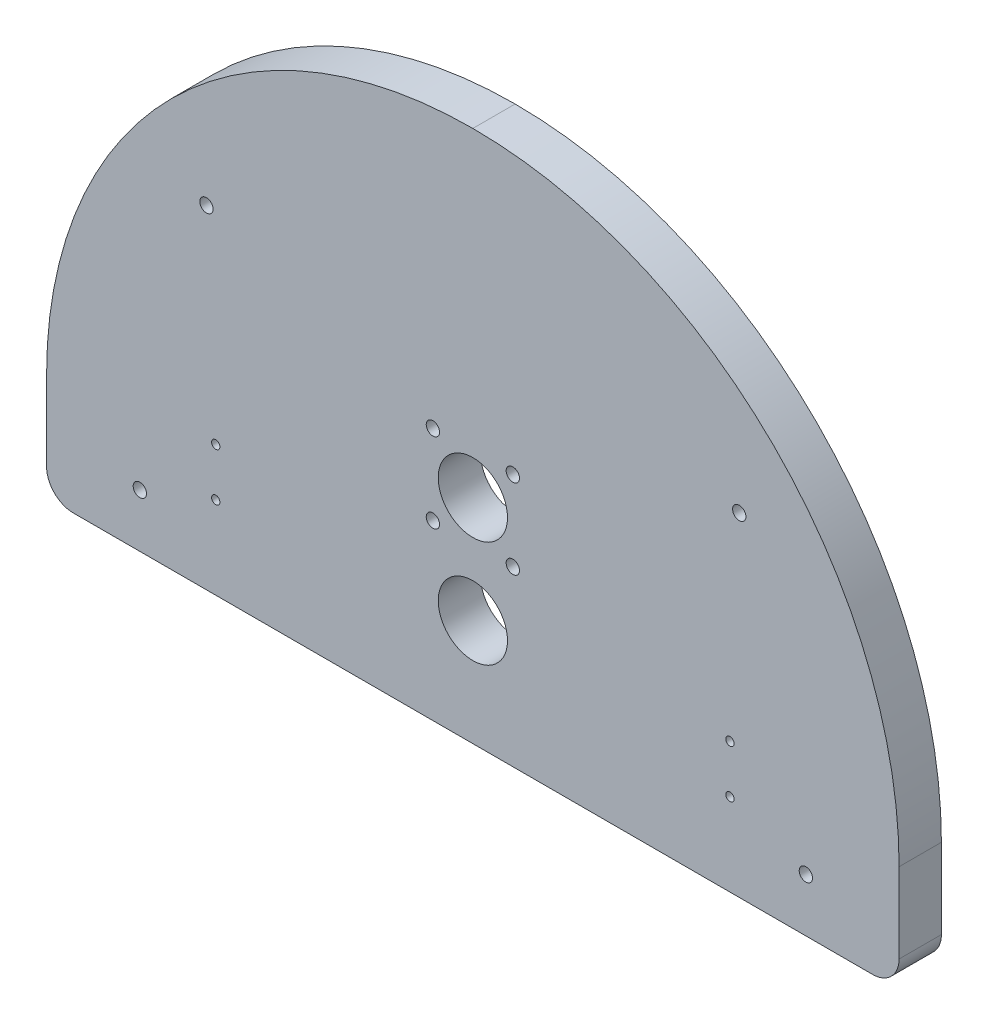
SolidWorks part; units mm, degrees
ref_plane "Front Plane" through (0, 0, 0) normal (0, 0, 1) x (1, 0, 0)
ref_plane "Top Plane" through (0, 0, 0) normal (0, 1, 0) x (1, 0, 0)
ref_plane "Right Plane" through (0, 0, 0) normal (1, 0, 0) x (0, 0, -1)
sketch "Sketch1" plane through (0, 0, 0) normal (0, 0, 1) x (1, 0, 0)
  line L1 (-160, 100) -> (160, 100)
  line L2 (-160, 100) -> (-160, -100)
  line L3 (-160, -100) -> (160, -100)
  line L4 (160, 100) -> (160, -100)
  line L5 (-160, 100) -> (160, -100) construction
  line L6 (-160, -100) -> (160, 100) construction
  point P0 (0, 0)
  dimension "D1" = 320
  dimension "D2" = 200
extrude "Boss-Extrude1" add sketch "Sketch1" along normal blind 15.875
fillet "Fillet1" radius 160 2 edges at (-160, 100, 7.9375) (160, 100, 7.9375)
fillet "Fillet2" radius 10 2 edges at (-160, -100, 7.9375) (160, -100, 7.9375)
sketch "Sketch2" plane through (0, 0, 15.875) normal (0, 0, 1) x (1, 0, 0)
  line L0 (-150, -100) -> (150, -100) construction
  circle A0 centre (0, -60) radius 13
  circle A1 centre (0, -20) radius 13
  dimension "D2" = 40
  dimension "D3" = 26
  dimension "D1" = 40
extrude "Cut-Extrude1" cut sketch "Sketch2" against normal through all
sketch "Sketch3" plane through (0, 0, 15.875) normal (0, 0, 1) x (1, 0, 0)
  line L1 (-15, -35) -> (15, -35) construction
  line L2 (-15, -35) -> (-15, -5) construction
  line L3 (-15, -5) -> (15, -5) construction
  line L4 (15, -35) -> (15, -5) construction
  line L5 (-15, -35) -> (15, -5) construction
  line L6 (-15, -5) -> (15, -35) construction
  circle A0 centre (-15, -5) radius 2.5
  circle A1 centre (-15, -35) radius 2.5
  circle A2 centre (15, -35) radius 2.5
  circle A3 centre (15, -5) radius 2.5
  point P0 (0, -20)
  dimension "D2" = 5
  dimension "D1" = 30
extrude "Cut-Extrude2" cut sketch "Sketch3" against normal through all
sketch "Sketch4" plane through (0, 0, 15.875) normal (0, 0, 1) x (1, 0, 0)
  line L0 (-125, -80) -> (125, -80) construction
  line L1 (100, 25) -> (-100, 25) construction
  line L2 (0, 25) -> (0, -80) construction
  line L3 (-150, -100) -> (150, -100) construction
  circle A0 centre (-100, 25) radius 2.5
  circle A1 centre (100, 25) radius 2.5
  circle A2 centre (125, -80) radius 2.5
  circle A3 centre (-125, -80) radius 2.5
  dimension "D5" = 5
  dimension "D1" = 20
  dimension "D2" = 125
  dimension "D3" = 200
  dimension "D4" = 250
extrude "Cut-Extrude3" cut sketch "Sketch4" against normal through all
sketch "Sketch5" plane through (0, 0, 0) normal (0, 0, -1) x (-1, 0, 0)
  circle A0 centre (96.5, -51) radius 1.5625
  circle A1 centre (96.5, -69) radius 1.5625
  circle A2 centre (-96.5, -51) radius 1.5625
  circle A3 centre (-96.5, -69) radius 1.5625
  dimension "D1" = 3.125
extrude "Cut-Extrude4" cut sketch "Sketch5" against normal through all
